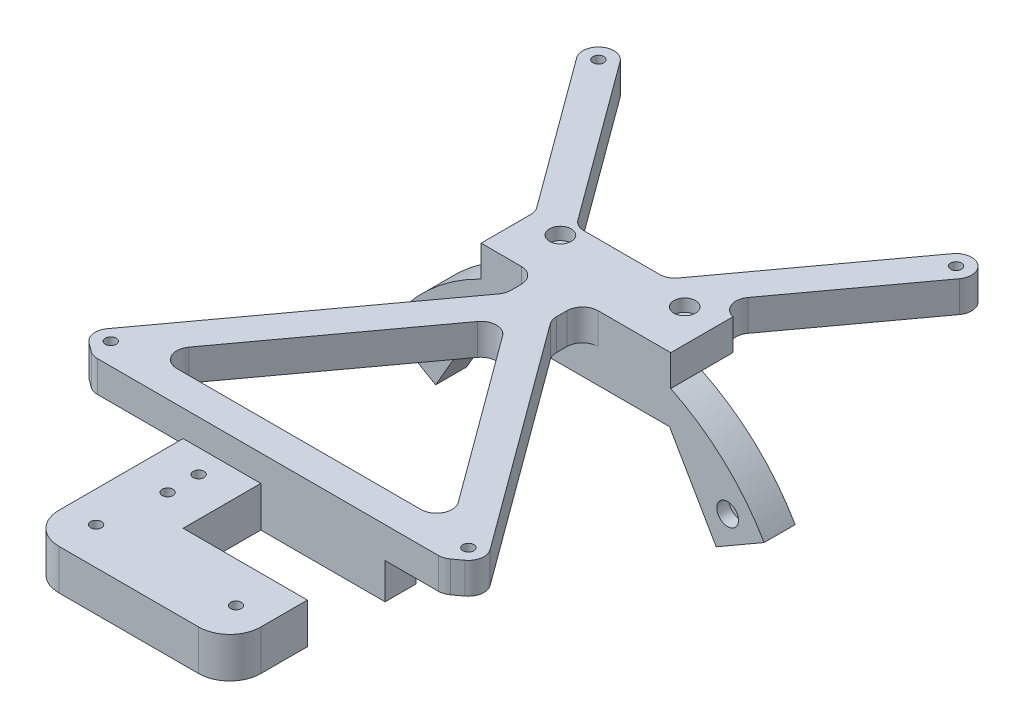
SolidWorks part; units mm, degrees
ref_plane "Plan de face" through (0, 0, 0) normal (0, 0, 1) x (1, 0, 0)
ref_plane "Plan de dessus" through (0, 0, 0) normal (0, 1, 0) x (1, 0, 0)
ref_plane "Plan de droite" through (0, 0, 0) normal (1, 0, 0) x (0, 0, -1)
sketch "Esquisse1" plane through (0, 0, 0) normal (0, 0, 1) x (1, 0, 0)
  line L0 (-30.13, 52.18) -> (30.13, 52.18)
  line L1 (30.13, 52.18) -> (45.13, 26.1992)
  line L2 (45.13, 26.1992) -> (60.5596, 35.1075)
  line L3 (-30.13, 52.18) -> (-45.13, 26.1992)
  line L4 (-45.13, 26.1992) -> (-60.5596, 35.1075)
  line L5 (-30.5123, 63) -> (30.5123, 63)
  circle A0 centre (0, 0) radius 70 construction
  arc A1 (-60.5596, 35.1075) -> (-30.5123, 63) centre (0, 0) cw
  arc A2 (60.5596, 35.1075) -> (30.5123, 63) centre (0, 0) ccw
  point P5 (0, 52.18)
  point P12 (0, 63)
  dimension "D1" = 140
  dimension "D2" = 120
  dimension "D3" = 30
  dimension "D4" = 60.26
  dimension "D5" = 61.0246
  dimension "D6" = 10.82
extrude "Boss.-Extru.1" add sketch "Esquisse1" along normal blind 10
sketch "Esquisse2" plane through (0, 63, 0) normal (0, 1, 0) x (1, 0, 0)
  line L0 (-30.5123, -10) -> (-30.5123, 0) construction
  line L1 (30.5123, -10) -> (-30.5123, -10)
  line L2 (30.5123, -10) -> (30.5123, 10)
  line L3 (30.5123, 10) -> (-30.5123, 10)
  line L4 (-30.5123, -10) -> (-30.5123, 10)
  line L5 (30.5123, 0) -> (-30.5123, 0) construction
  dimension "D1" = 10
extrude "Boss.-Extru.2" add sketch "Esquisse2" along normal blind 10
sketch "Esquisse3" plane through (0, 73, 0) normal (0, 1, 0) x (1, 0, 0)
  line L0 (30.5123, 0) -> (-30.5123, 0) construction
  line L1 (30.5123, -10) -> (30.5123, 10) construction
  line L2 (-30.5123, 10) -> (-30.5123, -10) construction
  line L3 (0, 0) -> (0, 10) construction
  line L4 (30.5123, 10) -> (-30.5123, 10) construction
  line L5 (20, 5) -> (-20, 5) construction
  circle A0 centre (20, 5) radius 1.75
  circle A1 centre (-20, 5) radius 1.75
  point P14 (0, 5)
  point P15 (0, 5)
  dimension "D1" = 3.5
  dimension "D2" = 20
extrude "Enlèv. mat.-Extru.1" cut sketch "Esquisse3" against normal up to next
sketch "Esquisse4" plane through (0, 73, 0) normal (0, 1, 0) x (1, 0, 0)
  circle A0 centre (20, 5) radius 3.5
  circle A1 centre (-20, 5) radius 3.5
  dimension "D1" = 7
extrude "Enlèv. mat.-Extru.2" cut sketch "Esquisse4" against normal blind 4
sketch "Esquisse5" plane through (0, 0, 10) normal (0, 0, 1) x (1, 0, 0)
  line L0 (-41.2992, 32.8344) -> (-56.3527, 41.5256) construction
  line L1 (-45.13, 26.1992) -> (-30.13, 52.18) construction
  line L2 (41.2992, 32.8344) -> (56.3527, 41.5256) construction
  line L3 (30.13, 52.18) -> (45.13, 26.1992) construction
  line L4 (-48.8259, 37.18) -> (48.8259, 37.18) construction
  line L5 (0, 52.18) -> (0, 37.18) construction
  line L6 (-30.13, 52.18) -> (30.13, 52.18) construction
  line L7 (-60.5596, 35.1075) -> (-45.13, 26.1992) construction
  line L8 (45.13, 26.1992) -> (60.5596, 35.1075) construction
  arc A0 (-30.5123, 63) -> (-60.5596, 35.1075) centre (0, 0) ccw construction
  arc A1 (60.5596, 35.1075) -> (30.5123, 63) centre (0, 0) ccw construction
  circle A2 centre (-48.8259, 37.18) radius 1.75
  circle A3 centre (48.8259, 37.18) radius 1.75
  dimension "D2" = 3.5
  dimension "D1" = 15
extrude "Enlèv. mat.-Extru.3" cut sketch "Esquisse5" against normal up to next
sketch "Esquisse6" plane through (0, 0, 10) normal (0, 0, 1) x (1, 0, 0)
  circle A0 centre (-48.8259, 37.18) radius 3.5
  circle A1 centre (48.8259, 37.18) radius 3.5
  dimension "D1" = 7
extrude "Enlèv. mat.-Extru.4" cut sketch "Esquisse6" against normal blind 4
sketch "Esquisse7" plane through (0, 73, 0) normal (0, 1, 0) x (1, 0, 0)
  line L0 (0, -10) -> (0, 10) construction
  line L1 (-30.5123, -10) -> (30.5123, -10) construction
  line L2 (30.5123, 10) -> (-30.5123, 10) construction
  line L3 (-62.77, -96.9) -> (52.31, 60) construction
  line L4 (52.31, -96.9) -> (-62.77, 60) construction
  line L5 (2.1076, -10) -> (2.1076, -20)
  line L6 (2.1076, -20) -> (59.2989, -97.9746)
  line L7 (59.2989, -97.9746) -> (51.2354, -103.8889)
  line L8 (51.2354, -103.8889) -> (-5.23, -26.9041)
  line L9 (-5.23, -26.9041) -> (-61.6954, -103.8889)
  line L10 (-61.6954, -103.8889) -> (-69.7589, -97.9746)
  line L11 (-69.7589, -97.9746) -> (-12.5676, -20)
  line L12 (-12.5676, -20) -> (-12.5676, -10)
  line L13 (52.31, -96.9) -> (55.2672, -100.9318) construction
  line L14 (-62.77, -96.9) -> (-65.7272, -100.9318) construction
  line L15 (9.4362, 10) -> (21.8377, 10)
  line L16 (21.8377, 10) -> (59.2989, 61.0746)
  line L17 (59.2989, 61.0746) -> (51.2354, 66.9889)
  line L18 (51.2354, 66.9889) -> (9.4362, 10)
  line L19 (52.31, 60) -> (55.2672, 64.0318) construction
  line L20 (-19.8962, 10) -> (-61.6954, 66.9889)
  line L21 (-61.6954, 66.9889) -> (-69.7589, 61.0746)
  line L22 (-69.7589, 61.0746) -> (-30.5123, 7.5658)
  line L23 (-30.5123, 10) -> (-30.5123, -10) construction
  line L24 (-30.5123, 7.5658) -> (-30.5123, 10)
  line L25 (-30.5123, 10) -> (-19.8962, 10)
  line L26 (-62.77, 60) -> (-65.7272, 64.0318) construction
  line L27 (2.1076, -10) -> (-12.5676, -10)
  circle A0 centre (52.31, -96.9) radius 1.75
  circle A1 centre (-62.77, -96.9) radius 1.75
  circle A2 centre (-62.77, 60) radius 1.75
  circle A3 centre (52.31, 60) radius 1.75
  point P10 (-5.23, -18.45)
  point P11 (-5.23, -18.45)
  dimension "D5" = 3.5
  dimension "D1" = 156.9
  dimension "D2" = 115.08
  dimension "D3" = 5.23
  dimension "D4" = 5
  dimension "D6" = 10
  dimension "D7" = 10
  dimension "D8" = 50
extrude "Boss.-Extru.3" add sketch "Esquisse7" against normal up to surface (10 mm away) up to face at (20, 63, -3.25)
sketch "Esquisse8" plane through (0, 73, 0) normal (0, 1, 0) x (1, 0, 0)
  line L0 (51.2354, -103.8889) -> (43.9008, -93.8889)
  line L1 (-5.23, -26.9041) -> (51.2354, -103.8889) construction
  line L2 (43.9008, -93.8889) -> (-54.3608, -93.8889)
  line L3 (-61.6954, -103.8889) -> (-5.23, -26.9041) construction
  line L4 (-54.3608, -93.8889) -> (-61.6954, -103.8889)
  line L5 (-61.6954, -103.8889) -> (51.2354, -103.8889)
  dimension "D1" = 10
extrude "Boss.-Extru.4" add sketch "Esquisse8" against normal up to surface (10 mm away) up to face at (-5.23, 63, 54.5146)
sketch "Esquisse9" plane through (0, 63, 0) normal (0, -1, 0) x (-1, 0, 0)
  circle A0 centre (-52.31, -96.9) radius 3.5
  circle A1 centre (62.77, -96.9) radius 3.5
  circle A2 centre (62.77, 60) radius 3.5
  circle A3 centre (-52.31, 60) radius 3.5
  dimension "D1" = 7
extrude "Enlèv. mat.-Extru.5" cut sketch "Esquisse9" against normal blind 3
ref_plane "Plan1" through (0, 64.5, 0) normal (0, -1, 0) x (-1, 0, 0)
sketch "Esquisse10" plane through (0, 64.5, 0) normal (0, -1, 0) x (-1, 0, 0)
  line L0 (54.3608, -93.8889) -> (-43.9008, -93.8889) construction
  line L1 (32.5, -153.8889) -> (-32.5, -153.8889)
  line L2 (32.5, -153.8889) -> (32.5, -93.8889)
  line L3 (32.5, -93.8889) -> (-32.5, -93.8889)
  line L4 (-32.5, -153.8889) -> (-32.5, -93.8889)
  line L5 (-51.2354, -103.8889) -> (61.6954, -103.8889) construction
  point P8 (5.23, -93.8889)
  point P9 (0, -93.8889)
  dimension "D1" = 65
  dimension "D2" = 50
  dimension "D3" = 5.23
extrude "Boss.-Extru.5" add sketch "Esquisse10" along normal blind 13
sketch "Esquisse11" plane through (0, 51.5, 0) normal (0, -1, 0) x (1, 0, 0)
  line L0 (-22.5, 141.8889) -> (22.5, 141.8889) construction
  line L1 (32.5, 153.8889) -> (-32.5, 153.8889) construction
  circle A0 centre (-22.5, 141.8889) radius 1.75
  circle A1 centre (22.5, 141.8889) radius 1.75
  point P4 (0, 141.8889)
  point P7 (0, 153.8889)
  dimension "D2" = 3.5
  dimension "D1" = 45
  dimension "D3" = 12
extrude "Enlèv. mat.-Extru.6" cut sketch "Esquisse11" against normal up to next
sketch "Esquisse12" plane through (0, 51.5, 0) normal (0, -1, 0) x (1, 0, 0)
  circle A0 centre (-22.5, 141.8889) radius 3.5
  circle A1 centre (22.5, 141.8889) radius 3.5
  dimension "D1" = 7
extrude "Enlèv. mat.-Extru.7" cut sketch "Esquisse12" against normal blind 4.75
fillet "Congé1" radius 10 2 edges at (32.5, 58, 153.8889) (-32.5, 58, 153.8889)
fillet "Congé2" radius 5 19 edges at (-54.3608, 68, 93.8889) (43.9008, 68, 93.8889) (59.2989, 68, 97.9746) (51.2354, 68, 103.8889) (-5.23, 68, 26.9041) (9.4362, 68, -10) (-19.8962, 68, -10) (2.1076, 68, 20) (2.1076, 68, 10) (21.8377, 68, -10) (59.2989, 68, -61.0746) (51.2354, 68, -66.9889) (-61.6954, 68, -66.9889) (-69.7589, 68, -61.0746) (-30.5123, 68, -7.5658) (-12.5676, 68, 20) (-12.5676, 68, 10) (-61.6954, 68, 103.8889) (-69.7589, 68, 97.9746)
sketch "Esquisse13" plane through (0, 64.5, 0) normal (0, 1, 0) x (1, 0, 0)
  line L1 (32.5, -103.8889) -> (-7.5, -103.8889)
  line L2 (32.5, -103.8889) -> (32.5, -128.8889)
  line L3 (32.5, -128.8889) -> (-7.5, -128.8889)
  line L4 (-7.5, -103.8889) -> (-7.5, -128.8889)
  dimension "D1" = 25
  dimension "D2" = 40
extrude "Enlèv. mat.-Extru.8" cut sketch "Esquisse13" against normal up to next
sketch "Esquisse14" plane through (0, 51.5, 0) normal (0, -1, 0) x (1, 0, 0)
  line L0 (-7.5, 116.3889) -> (-32.5, 116.3889) construction
  line L1 (-7.5, 103.8889) -> (-7.5, 128.8889) construction
  line L2 (-32.5, 143.8889) -> (-32.5, 93.8889) construction
  line L3 (-20, 121.3889) -> (-20, 111.3889) construction
  circle A0 centre (-20, 121.3889) radius 1.75
  circle A1 centre (-20, 111.3889) radius 1.75
  point P11 (-20, 116.3889)
  point P12 (-20, 116.3889)
  dimension "D1" = 3.5
  dimension "D2" = 10
extrude "Enlèv. mat.-Extru.9" cut sketch "Esquisse14" against normal up to next
sketch "Esquisse15" plane through (0, 51.5, 0) normal (0, -1, 0) x (1, 0, 0)
  circle A0 centre (-20, 121.3889) radius 3.5
  circle A1 centre (-20, 111.3889) radius 3.5
  dimension "D1" = 7
extrude "Enlèv. mat.-Extru.10" cut sketch "Esquisse15" against normal offset from surface (7 mm away) 6 up to face at (-20, 64.5, 119.6389)
